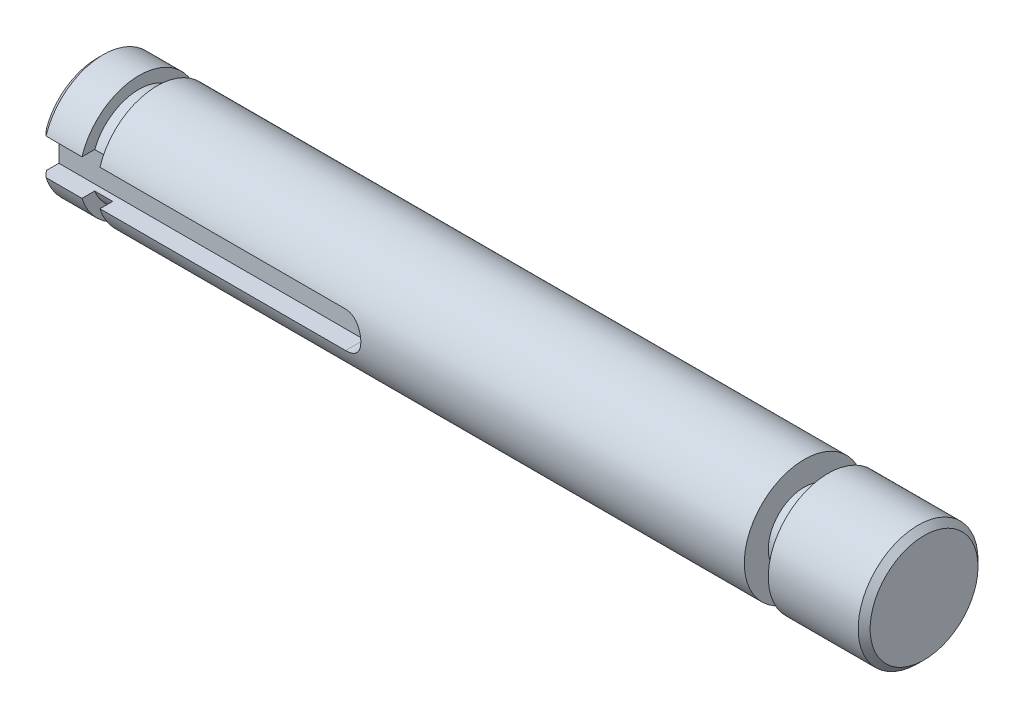
SolidWorks part; units mm, degrees
ref_plane "Front Plane" through (0, 0, 0) normal (0, 0, 1) x (1, 0, 0)
ref_plane "Top Plane" through (0, 0, 0) normal (0, 1, 0) x (1, 0, 0)
ref_plane "Right Plane" through (0, 0, 0) normal (1, 0, 0) x (0, 0, -1)
sketch "Sketch1" plane through (0, 0, 0) normal (1, 0, 0) x (0, 0, -1)
  circle A0 centre (0, 0) radius 5
  dimension "D1" = 10
extrude "Boss-Extrude1" add sketch "Sketch1" along normal mid plane 69
cosmetic thread "Cosmetic Thread1" parameters "D1"=7, "D2"=6.619
sketch "Sketch2" plane through (34.5, 0, 0) normal (1, 0, 0) x (0, 0, -1)
  circle A0 centre (0, 0) radius 3
  circle A1 centre (0, 0) radius 5
  circle A2 centre (0, 0) radius 5
  dimension "D2" = 6
  dimension "D1" = 0
extrude "Cut-Extrude1" cut sketch "Sketch2" along normal blind 2 from offset 10 offset against normal yes
sketch "Sketch3" plane through (-34.5, 0, 0) normal (-1, 0, 0) x (0, 0, 1)
  circle A0 centre (0, 0) radius 4
  circle A1 centre (0, 0) radius 5
  circle A2 centre (0, 0) radius 5
  dimension "D2" = 8
  dimension "D1" = 0
extrude "Cut-Extrude2" cut sketch "Sketch3" along normal blind 1.5 from offset 5 offset against normal yes
chamfer "Chamfer1" distance 0.5 angle 45 2 edges at (34.5, 0, -5) (-34.5, 0, -5)
sketch "Sketch4" plane through (0, 0, 0) normal (0, 0, 1) x (1, 0, 0)
  line L0 (-34.5, 0) -> (-9, 0) construction
  line L1 (-34.5, 4.5) -> (-34.5, -4.5) construction
  line L2 (-34.5, 1.5) -> (-9, 1.5)
  line L3 (-34.5, -1.5) -> (-9, -1.5)
  line L4 (-34.5, 1.5) -> (-34.5, -1.5)
  arc A1 (-9, -1.5) -> (-9, 1.5) centre (-9, 0) ccw
  point P5 (-21.7205, 0)
  dimension "D2" = 1.5
  dimension "D1" = 25.5
  dimension "D3" = 3
  dimension "D4" = 1.5
extrude "Cut-Extrude3" cut sketch "Sketch4" along normal through all from offset 3.2
